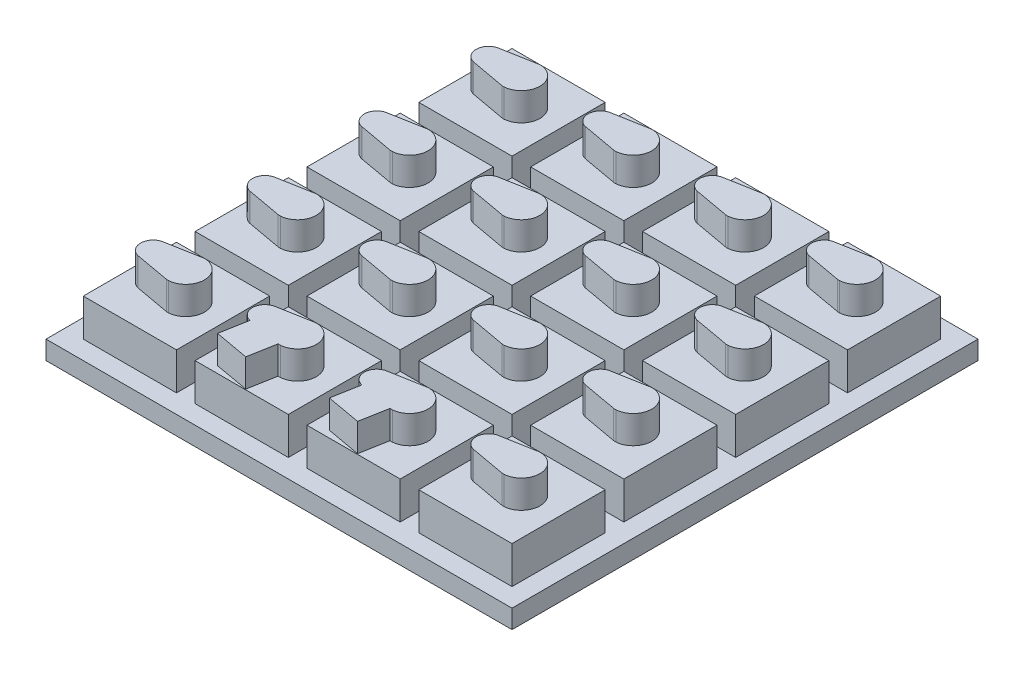
SolidWorks part; units mm, degrees
ref_plane "Front Plane" through (0, 0, 0) normal (0, 0, 1) x (1, 0, 0)
ref_plane "Top Plane" through (0, 0, 0) normal (0, 1, 0) x (1, 0, 0)
ref_plane "Right Plane" through (0, 0, 0) normal (1, 0, 0) x (0, 0, -1)
sketch "Sketch1" plane through (0, 0, 0) normal (0, 1, 0) x (1, 0, 0)
  line L0 (0, 0) -> (-49.3047, 0) construction
  line L1 (-42, 31) -> (-42, 33)
  line L2 (-42, 33) -> (-46, 33)
  line L3 (-46, 33) -> (-46, 29)
  line L4 (-46, 29) -> (-44, 29)
  line L5 (-44, 29) -> (-44, 31)
  line L6 (4, 33) -> (4, 31)
  line L7 (4, 31) -> (6, 31)
  line L8 (6, 29) -> (8, 29)
  line L9 (-8, 5) -> (-18, 5) construction
  line L10 (-8, 7) -> (-15.8633, 7) construction
  line L11 (-8, 17) -> (-14.8417, 17) construction
  line L12 (-8, -5) -> (-16.8168, -5) construction
  line L13 (-8, 29) -> (-13.8882, 29) construction
  line L14 (-8, 19) -> (-12, 19) construction
  line L15 (-8, -7) -> (-15.1823, -7) construction
  line L16 (-8, -17) -> (-14.6374, -17) construction
  line L17 (8, 29) -> (8, 33)
  line L18 (-42, 29) -> (-32, 29)
  line L19 (-42, 29) -> (-42, 19)
  line L20 (-42, 19) -> (-32, 19)
  line L21 (-32, 29) -> (-32, 19)
  line L22 (-30, 29) -> (-20, 29)
  line L23 (-30, 29) -> (-30, 19)
  line L24 (-30, 19) -> (-20, 19)
  line L25 (-20, 29) -> (-20, 19)
  line L26 (-18, 29) -> (-8, 29)
  line L27 (-18, 29) -> (-18, 19)
  line L28 (-18, 19) -> (-8, 19)
  line L29 (-8, 29) -> (-8, 19)
  line L30 (-6, 29) -> (4, 29)
  line L31 (-6, 29) -> (-6, 19)
  line L32 (-6, 19) -> (4, 19)
  line L33 (4, 29) -> (4, 19)
  line L34 (-32, 17) -> (-42, 17)
  line L35 (-32, 17) -> (-32, 7)
  line L36 (-32, 7) -> (-42, 7)
  line L37 (-42, 17) -> (-42, 7)
  line L38 (-30, 17) -> (-20, 17)
  line L39 (-30, 17) -> (-30, 7)
  line L40 (-30, 7) -> (-20, 7)
  line L41 (-20, 17) -> (-20, 7)
  line L42 (-18, 7) -> (-8, 7)
  line L43 (-18, 7) -> (-18, 17)
  line L44 (-18, 17) -> (-8, 17)
  line L45 (-8, 7) -> (-8, 17)
  line L46 (-6, 17) -> (4, 17)
  line L47 (-6, 17) -> (-6, 7)
  line L48 (-6, 7) -> (4, 7)
  line L49 (4, 17) -> (4, 7)
  line L50 (-6, 5) -> (4, 5)
  line L51 (-6, 5) -> (-6, -5)
  line L52 (-6, -5) -> (4, -5)
  line L53 (4, 5) -> (4, -5)
  line L54 (-18, -5) -> (-8, -5)
  line L55 (-18, -5) -> (-18, 5)
  line L56 (-18, 5) -> (-8, 5)
  line L57 (-8, -5) -> (-8, 5)
  line L58 (-20, 5) -> (-30, 5)
  line L59 (-20, 5) -> (-20, -5)
  line L60 (-20, -5) -> (-30, -5)
  line L61 (-30, 5) -> (-30, -5)
  line L62 (-32, -5) -> (-42, -5)
  line L63 (-32, -5) -> (-32, 5)
  line L64 (-32, 5) -> (-42, 5)
  line L65 (-42, -5) -> (-42, 5)
  line L66 (-42, -7) -> (-32, -7)
  line L67 (-42, -7) -> (-42, -17)
  line L68 (-42, -17) -> (-32, -17)
  line L69 (-32, -7) -> (-32, -17)
  line L70 (-30, -7) -> (-20, -7)
  line L71 (-30, -7) -> (-30, -17)
  line L72 (-30, -17) -> (-20, -17)
  line L73 (-20, -7) -> (-20, -17)
  line L74 (-18, -7) -> (-8, -7)
  line L75 (-18, -7) -> (-18, -17)
  line L76 (-18, -17) -> (-8, -17)
  line L77 (-8, -7) -> (-8, -17)
  line L78 (-6, -7) -> (4, -7)
  line L79 (-6, -7) -> (-6, -17)
  line L80 (-6, -17) -> (4, -17)
  line L81 (4, -7) -> (4, -17)
  line L82 (-44, 31) -> (6, 31)
  line L83 (-44, 31) -> (-44, -19)
  line L84 (-44, -19) -> (6, -19)
  line L85 (6, 31) -> (6, -19)
  line L86 (8, 33) -> (4, 33)
  line L87 (4, -19) -> (4, -21)
  line L88 (4, -21) -> (8, -21)
  line L89 (8, -21) -> (8, -17)
  line L90 (8, -17) -> (6, -17)
  line L91 (6, -17) -> (6, -19)
  line L92 (-42, -21) -> (-46, -21)
  line L93 (-46, -21) -> (-46, -17)
  line L94 (-46, -17) -> (-44, -17)
  line L95 (-44, -17) -> (-44, -19)
  line L96 (-42, -19) -> (-42, -21)
  point P1 (-12, 12)
  point P3 (-12, 0)
  point P8 (-24, 0)
  point P10 (0, 24)
  point P11 (-24, 12)
  point P12 (0, 12)
  point P13 (0, -12)
  point P14 (-12, -12)
  point P16 (-24, -12)
  point P19 (-36, 12)
  point P21 (-36, 24)
  point P22 (-24, 24)
  point P23 (-12, 24)
  point P24 (-36, 0)
  point P25 (-36, -12)
  point P32 (8, 29)
  point P34 (4, 33)
  point P35 (8, 33)
  point P36 (-46, -19)
  point P37 (-46, -21)
  point P38 (-42, -21)
  point P39 (4, -21)
  point P40 (8, -21)
  point P41 (8, -17)
  line B0 (-0.1035, 1.9813) -> (-3.7918, 1.315)
  line B1 (-3.7918, -1.315) -> (-0.1035, -1.9813)
  arc B2 (-3.9397, 1.2764) -> (-3.9397, -1.2764) centre (-3.5, 0) ccw
  arc B3 (0.1486, 1.9945) -> (0.1486, -1.9945) centre (0, 0) cw
  arc B4 (-3.9397, 1.2764) -> (-3.7918, 1.315) centre (-3.614, 0.3309) cw
  arc B5 (-3.7918, -1.315) -> (-3.9397, -1.2764) centre (-3.614, -0.3309) cw
  arc B6 (0.1486, 1.9945) -> (-0.1035, 1.9813) centre (0.0743, 0.9972) ccw
  arc B7 (0.1486, -1.9945) -> (-0.1035, -1.9813) centre (0.0743, -0.9972) cw
  line B8 (-12.1035, 1.9813) -> (-15.7918, 1.315)
  line B9 (-15.7918, -1.315) -> (-12.1035, -1.9813)
  arc B10 (-15.9397, 1.2764) -> (-15.9397, -1.2764) centre (-15.5, 0) ccw
  arc B11 (-11.8514, 1.9945) -> (-11.8514, -1.9945) centre (-12, 0) cw
  arc B12 (-15.9397, 1.2764) -> (-15.7918, 1.315) centre (-15.614, 0.3309) cw
  arc B13 (-15.7918, -1.315) -> (-15.9397, -1.2764) centre (-15.614, -0.3309) cw
  arc B14 (-11.8514, 1.9945) -> (-12.1035, 1.9813) centre (-11.9257, 0.9972) ccw
  arc B15 (-11.8514, -1.9945) -> (-12.1035, -1.9813) centre (-11.9257, -0.9972) cw
  line B16 (-24.1035, 1.9813) -> (-27.7918, 1.315)
  line B17 (-27.7918, -1.315) -> (-24.1035, -1.9813)
  arc B18 (-27.9397, 1.2764) -> (-27.9397, -1.2764) centre (-27.5, 0) ccw
  arc B19 (-23.8514, 1.9945) -> (-23.8514, -1.9945) centre (-24, 0) cw
  arc B20 (-27.9397, 1.2764) -> (-27.7918, 1.315) centre (-27.614, 0.3309) cw
  arc B21 (-27.7918, -1.315) -> (-27.9397, -1.2764) centre (-27.614, -0.3309) cw
  arc B22 (-23.8514, 1.9945) -> (-24.1035, 1.9813) centre (-23.9257, 0.9972) ccw
  arc B23 (-23.8514, -1.9945) -> (-24.1035, -1.9813) centre (-23.9257, -0.9972) cw
  line B24 (-0.1035, 13.9813) -> (-3.7918, 13.315)
  line B25 (-3.7918, 10.685) -> (-0.1035, 10.0187)
  arc B26 (-3.9397, 13.2764) -> (-3.9397, 10.7236) centre (-3.5, 12) ccw
  arc B27 (0.1486, 13.9945) -> (0.1486, 10.0055) centre (0, 12) cw
  arc B28 (-3.9397, 13.2764) -> (-3.7918, 13.315) centre (-3.614, 12.3309) cw
  arc B29 (-3.7918, 10.685) -> (-3.9397, 10.7236) centre (-3.614, 11.6691) cw
  arc B30 (0.1486, 13.9945) -> (-0.1035, 13.9813) centre (0.0743, 12.9972) ccw
  arc B31 (0.1486, 10.0055) -> (-0.1035, 10.0187) centre (0.0743, 11.0028) cw
  line B32 (-12.1035, 13.9813) -> (-15.7918, 13.315)
  line B33 (-15.7918, 10.685) -> (-12.1035, 10.0187)
  arc B34 (-15.9397, 13.2764) -> (-15.9397, 10.7236) centre (-15.5, 12) ccw
  arc B35 (-11.8514, 13.9945) -> (-11.8514, 10.0055) centre (-12, 12) cw
  arc B36 (-15.9397, 13.2764) -> (-15.7918, 13.315) centre (-15.614, 12.3309) cw
  arc B37 (-15.7918, 10.685) -> (-15.9397, 10.7236) centre (-15.614, 11.6691) cw
  arc B38 (-11.8514, 13.9945) -> (-12.1035, 13.9813) centre (-11.9257, 12.9972) ccw
  arc B39 (-11.8514, 10.0055) -> (-12.1035, 10.0187) centre (-11.9257, 11.0028) cw
  line B40 (-24.1035, 13.9813) -> (-27.7918, 13.315)
  line B41 (-27.7918, 10.685) -> (-24.1035, 10.0187)
  arc B42 (-27.9397, 13.2764) -> (-27.9397, 10.7236) centre (-27.5, 12) ccw
  arc B43 (-23.8514, 13.9945) -> (-23.8514, 10.0055) centre (-24, 12) cw
  arc B44 (-27.9397, 13.2764) -> (-27.7918, 13.315) centre (-27.614, 12.3309) cw
  arc B45 (-27.7918, 10.685) -> (-27.9397, 10.7236) centre (-27.614, 11.6691) cw
  arc B46 (-23.8514, 13.9945) -> (-24.1035, 13.9813) centre (-23.9257, 12.9972) ccw
  arc B47 (-23.8514, 10.0055) -> (-24.1035, 10.0187) centre (-23.9257, 11.0028) cw
  line B48 (-12.1035, -10.0187) -> (-15.7918, -10.685)
  line B49 (-15.7918, -13.315) -> (-12.1035, -13.9813)
  arc B50 (-15.9397, -10.7236) -> (-15.9397, -13.2764) centre (-15.5, -12) ccw
  arc B51 (-11.8514, -10.0055) -> (-11.8514, -13.9945) centre (-12, -12) cw
  arc B52 (-15.9397, -10.7236) -> (-15.7918, -10.685) centre (-15.614, -11.6691) cw
  arc B53 (-15.7918, -13.315) -> (-15.9397, -13.2764) centre (-15.614, -12.3309) cw
  arc B54 (-11.8514, -10.0055) -> (-12.1035, -10.0187) centre (-11.9257, -11.0028) ccw
  arc B55 (-11.8514, -13.9945) -> (-12.1035, -13.9813) centre (-11.9257, -12.9972) cw
  line B56 (-0.1035, -10.0187) -> (-3.7918, -10.685)
  line B57 (-3.7918, -13.315) -> (-0.1035, -13.9813)
  arc B58 (-3.9397, -10.7236) -> (-3.9397, -13.2764) centre (-3.5, -12) ccw
  arc B59 (0.1486, -10.0055) -> (0.1486, -13.9945) centre (0, -12) cw
  arc B60 (-3.9397, -10.7236) -> (-3.7918, -10.685) centre (-3.614, -11.6691) cw
  arc B61 (-3.7918, -13.315) -> (-3.9397, -13.2764) centre (-3.614, -12.3309) cw
  arc B62 (0.1486, -10.0055) -> (-0.1035, -10.0187) centre (0.0743, -11.0028) ccw
  arc B63 (0.1486, -13.9945) -> (-0.1035, -13.9813) centre (0.0743, -12.9972) cw
  line B64 (-24.1035, -10.0187) -> (-27.7918, -10.685)
  line B65 (-27.7918, -13.315) -> (-24.1035, -13.9813)
  arc B66 (-27.9397, -10.7236) -> (-27.9397, -13.2764) centre (-27.5, -12) ccw
  arc B67 (-23.8514, -10.0055) -> (-23.8514, -13.9945) centre (-24, -12) cw
  arc B68 (-27.9397, -10.7236) -> (-27.7918, -10.685) centre (-27.614, -11.6691) cw
  arc B69 (-27.7918, -13.315) -> (-27.9397, -13.2764) centre (-27.614, -12.3309) cw
  arc B70 (-23.8514, -10.0055) -> (-24.1035, -10.0187) centre (-23.9257, -11.0028) ccw
  arc B71 (-23.8514, -13.9945) -> (-24.1035, -13.9813) centre (-23.9257, -12.9972) cw
  line B72 (-0.1035, 25.9813) -> (-3.7918, 25.315)
  line B73 (-3.7918, 22.685) -> (-0.1035, 22.0187)
  arc B74 (-3.9397, 25.2764) -> (-3.9397, 22.7236) centre (-3.5, 24) ccw
  arc B75 (0.1486, 25.9945) -> (0.1486, 22.0055) centre (0, 24) cw
  arc B76 (-3.9397, 25.2764) -> (-3.7918, 25.315) centre (-3.614, 24.3309) cw
  arc B77 (-3.7918, 22.685) -> (-3.9397, 22.7236) centre (-3.614, 23.6691) cw
  arc B78 (0.1486, 25.9945) -> (-0.1035, 25.9813) centre (0.0743, 24.9972) ccw
  arc B79 (0.1486, 22.0055) -> (-0.1035, 22.0187) centre (0.0743, 23.0028) cw
  line B80 (-12.1035, 25.9813) -> (-15.7918, 25.315)
  line B81 (-15.7918, 22.685) -> (-12.1035, 22.0187)
  arc B82 (-15.9397, 25.2764) -> (-15.9397, 22.7236) centre (-15.5, 24) ccw
  arc B83 (-11.8514, 25.9945) -> (-11.8514, 22.0055) centre (-12, 24) cw
  arc B84 (-15.9397, 25.2764) -> (-15.7918, 25.315) centre (-15.614, 24.3309) cw
  arc B85 (-15.7918, 22.685) -> (-15.9397, 22.7236) centre (-15.614, 23.6691) cw
  arc B86 (-11.8514, 25.9945) -> (-12.1035, 25.9813) centre (-11.9257, 24.9972) ccw
  arc B87 (-11.8514, 22.0055) -> (-12.1035, 22.0187) centre (-11.9257, 23.0028) cw
  line B88 (-24.1035, 25.9813) -> (-27.7918, 25.315)
  line B89 (-27.7918, 22.685) -> (-24.1035, 22.0187)
  arc B90 (-27.9397, 25.2764) -> (-27.9397, 22.7236) centre (-27.5, 24) ccw
  arc B91 (-23.8514, 25.9945) -> (-23.8514, 22.0055) centre (-24, 24) cw
  arc B92 (-27.9397, 25.2764) -> (-27.7918, 25.315) centre (-27.614, 24.3309) cw
  arc B93 (-27.7918, 22.685) -> (-27.9397, 22.7236) centre (-27.614, 23.6691) cw
  arc B94 (-23.8514, 25.9945) -> (-24.1035, 25.9813) centre (-23.9257, 24.9972) ccw
  arc B95 (-23.8514, 22.0055) -> (-24.1035, 22.0187) centre (-23.9257, 23.0028) cw
  line B96 (-36.1035, -10.0187) -> (-39.7918, -10.685)
  line B97 (-39.7918, -13.315) -> (-36.1035, -13.9813)
  arc B98 (-39.9397, -10.7236) -> (-39.9397, -13.2764) centre (-39.5, -12) ccw
  arc B99 (-35.8514, -10.0055) -> (-35.8514, -13.9945) centre (-36, -12) cw
  arc B100 (-39.9397, -10.7236) -> (-39.7918, -10.685) centre (-39.614, -11.6691) cw
  arc B101 (-39.7918, -13.315) -> (-39.9397, -13.2764) centre (-39.614, -12.3309) cw
  arc B102 (-35.8514, -10.0055) -> (-36.1035, -10.0187) centre (-35.9257, -11.0028) ccw
  arc B103 (-35.8514, -13.9945) -> (-36.1035, -13.9813) centre (-35.9257, -12.9972) cw
  line B104 (-36.1035, 25.9813) -> (-39.7918, 25.315)
  line B105 (-39.7918, 22.685) -> (-36.1035, 22.0187)
  arc B106 (-39.9397, 25.2764) -> (-39.9397, 22.7236) centre (-39.5, 24) ccw
  arc B107 (-35.8514, 25.9945) -> (-35.8514, 22.0055) centre (-36, 24) cw
  arc B108 (-39.9397, 25.2764) -> (-39.7918, 25.315) centre (-39.614, 24.3309) cw
  arc B109 (-39.7918, 22.685) -> (-39.9397, 22.7236) centre (-39.614, 23.6691) cw
  arc B110 (-35.8514, 25.9945) -> (-36.1035, 25.9813) centre (-35.9257, 24.9972) ccw
  arc B111 (-35.8514, 22.0055) -> (-36.1035, 22.0187) centre (-35.9257, 23.0028) cw
  line B112 (-36.1035, 1.9813) -> (-39.7918, 1.315)
  line B113 (-39.7918, -1.315) -> (-36.1035, -1.9813)
  arc B114 (-39.9397, 1.2764) -> (-39.9397, -1.2764) centre (-39.5, 0) ccw
  arc B115 (-35.8514, 1.9945) -> (-35.8514, -1.9945) centre (-36, 0) cw
  arc B116 (-39.9397, 1.2764) -> (-39.7918, 1.315) centre (-39.614, 0.3309) cw
  arc B117 (-39.7918, -1.315) -> (-39.9397, -1.2764) centre (-39.614, -0.3309) cw
  arc B118 (-35.8514, 1.9945) -> (-36.1035, 1.9813) centre (-35.9257, 0.9972) ccw
  arc B119 (-35.8514, -1.9945) -> (-36.1035, -1.9813) centre (-35.9257, -0.9972) cw
  line B120 (-36.1035, 13.9813) -> (-39.7918, 13.315)
  line B121 (-39.7918, 10.685) -> (-36.1035, 10.0187)
  arc B122 (-39.9397, 13.2764) -> (-39.9397, 10.7236) centre (-39.5, 12) ccw
  arc B123 (-35.8514, 13.9945) -> (-35.8514, 10.0055) centre (-36, 12) cw
  arc B124 (-39.9397, 13.2764) -> (-39.7918, 13.315) centre (-39.614, 12.3309) cw
  arc B125 (-39.7918, 10.685) -> (-39.9397, 10.7236) centre (-39.614, 11.6691) cw
  arc B126 (-35.8514, 13.9945) -> (-36.1035, 13.9813) centre (-35.9257, 12.9972) ccw
  arc B127 (-35.8514, 10.0055) -> (-36.1035, 10.0187) centre (-35.9257, 11.0028) cw
sketch_block_instance "Block1-4"
sketch_block "Block1"
sketch_block_instance "Block1-6"
sketch_block_instance "Block1-7"
sketch_block_instance "Block1-8"
sketch_block_instance "Block1-9"
sketch_block_instance "Block1-10"
sketch_block_instance "Block1-14"
sketch_block_instance "Block1-15"
sketch_block_instance "Block1-16"
sketch_block_instance "Block1-17"
sketch_block_instance "Block1-18"
sketch_block_instance "Block1-19"
sketch_block_instance "Block1-20"
sketch_block_instance "Block1-21"
sketch_block_instance "Block1-22"
sketch_block_instance "Block1-23"
extrude "Boss-Extrude10" add sketch "Sketch1" along normal blind 9
extrude "Boss-Extrude11" add sketch "Sketch1<21>" along normal blind 6 contours L69 L66 L67 L68 B99 B103 B97 B101 B98 B100 B96 B102 | L65 L62 L63 L64 B115 B119 B113 B117 B114 B116 B112 B118 | L34 L37 L36 L35 B123 B127 B121 B125 B122 B124 B120 B126 | L21 L18 L19 L20 B107 B111 B105 B109 B106 B108 B104 B110 | L25 L22 L23 L24 B91 B95 B89 B93 B90 B92 B88 B94 | L41 L38 L39 L40 B43 B47 B41 B45 B42 B44 B40 B46 | L29 L26 L27 L28 B83 B87 B81 B85 B82 B84 B80 B86 | L33 L30 L31 L32 B75 B79 B73 B77 B74 B76 B72 B78 | L42 L45 L44 L43 B35 B39 B33 B37 B34 B36 B32 B38 | L49 L46 L47 L48 B27 B31 B25 B29 B26 B28 B24 B30 | L54 L57 L56 L55 B11 B15 B9 B13 B10 B12 B8 B14 | L58 L61 L60 L59 B19 B23 B17 B21 B18 B20 B16 B22 | L73 L70 L71 L72 B67 B71 B65 B69 B66 B68 B64 B70 | L77 L74 L75 L76 B51 B55 B49 B53 B50 B52 B48 B54 | L81 L78 L79 L80 B59 B63 B57 B61 B58 B60 B56 B62 | L53 L50 L51 L52 B3 B7 B1 B5 B2 B4 B0 B6 region at (-37, 0, -28.8586) region at (-25, 0, -28.8586) region at (-13, 0, -28.8586) region at (-1, 0, -28.8586) region at (-32.1414, 0, -12) region at (-25, 0, -16.8586) region at (-17.8586, 0, -12) region at (-1, 0, -16.8586) region at (-1, 0, -4.8586) region at (-17.8586, 0, 0) region at (-20.1414, 0, 0) region at (-37, 0, 4.8586) region at (-37, 0, 7.1414) region at (-25, 0, 7.1414) region at (-13, 0, 7.1414) region at (-1, 0, 7.1414)
sketch "Sketch1<21>" plane through (0, 0, 0) normal (0, 1, 0) x (1, 0, 0) same geometry as "Sketch1"
extrude "Boss-Extrude12" add sketch "Sketch1<22>" along normal blind 2 contours L85 L7 L82 L5 L83 L84 L74 L77 L76 L75 L66 L69 L68 L67 L50 L53 L52 L51 L38 L41 L40 L39 L37 L34 L35 L36 L26 L29 L28 L27 L18 L21 L20 L19 L22 L25 L24 region at (-19, 0, -6)
sketch "Sketch1<22>" plane through (0, 0, 0) normal (0, 1, 0) x (1, 0, 0) same geometry as "Sketch1"
sketch "Sketch5" plane through (-2.8285, 0, 15.6569) normal (-0.1778, 0, 0.9841) x (0.9841, 0, 0.1778)
  line L1 (-13.1731, 9) -> (-9.4251, 9)
  line L2 (-13.1731, 9) -> (-13.1731, 6)
  line L3 (-13.1731, 6) -> (-9.4251, 6)
  line L4 (-9.4251, 9) -> (-9.4251, 6)
extrude "Boss-Extrude13" add sketch "Sketch5" along normal blind 3
sketch "Sketch6" plane through (-3.2078, 0, 17.7563) normal (-0.1778, 0, 0.9841) x (0.9841, 0, 0.1778)
  line L1 (-24.9819, 9) -> (-21.2339, 9)
  line L2 (-24.9819, 9) -> (-24.9819, 6)
  line L3 (-24.9819, 6) -> (-21.2339, 6)
  line L4 (-21.2339, 9) -> (-21.2339, 6)
extrude "Boss-Extrude14" add sketch "Sketch6" along normal blind 3
